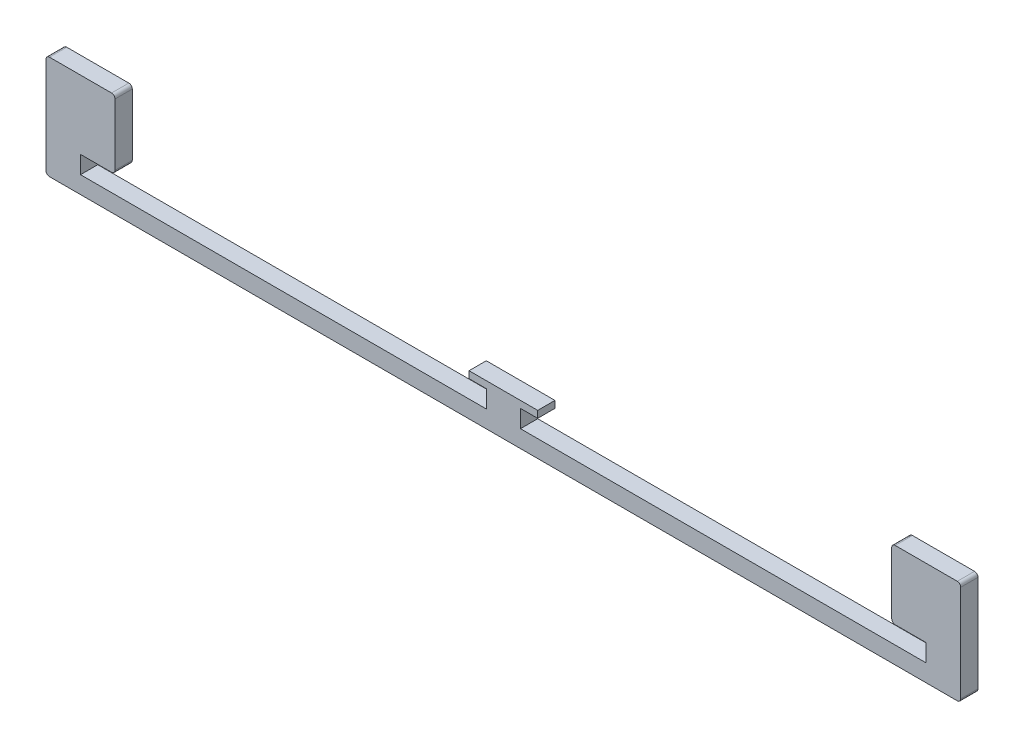
SolidWorks part; units mm, degrees
ref_plane "Front" through (0, 0, 0) normal (0, 0, 1) x (1, 0, 0)
ref_plane "Top" through (0, 0, 0) normal (0, 1, 0) x (1, 0, 0)
ref_plane "Right" through (0, 0, 0) normal (1, 0, 0) x (0, 0, -1)
sketch "Sketch1" plane through (0, 0, 0) normal (0, 0, 1) x (1, 0, 0)
  line L1 (0, 0) -> (132.55, 0)
  line L3 (10, 5) -> (127.6, 5)
  line L8 (10, 5) -> (10, 10.1)
  line L9 (10, 10.1) -> (20, 10.1)
  line L11 (0, 30) -> (20, 30)
  line L12 (20, 10.1) -> (20, 30)
  line L22 (127.6, 5) -> (127.6, 10.1)
  line L25 (122.6, 10.1) -> (127.6, 10.1)
  line L26 (122.6, 10.1) -> (122.6, 12.1)
  line L27 (122.6, 12.1) -> (132.55, 12.1)
  line L30 (0, 30) -> (0, 0)
  line L31 (132.55, 12.1) -> (132.55, 0)
  dimension "D2" = 5
  dimension "D3" = 5.1
  dimension "D4" = 4.95
  dimension "D5" = 117.6
  dimension "D8" = 30
  dimension "D9" = 10
  dimension "D10" = 20
  dimension "D14" = 5
  dimension "D15" = 2
  dimension "D16" = 5.1
extrude "Boss-Extrude1" add sketch "Sketch1" along normal blind 5
mirror "Mirror1" about plane through (132.55, 12.1, 5) normal (-1, 0, 0) of bodies 103
fillet "Fillet1" radius 1 8 edges at (265.1, 0, 2.5) (265.1, 30, 2.5) (245.1, 30, 2.5) (245.1, 10.1, 2.5) (0, 0, 2.5) (0, 30, 2.5) (20, 30, 2.5) (20, 10.1, 2.5)
